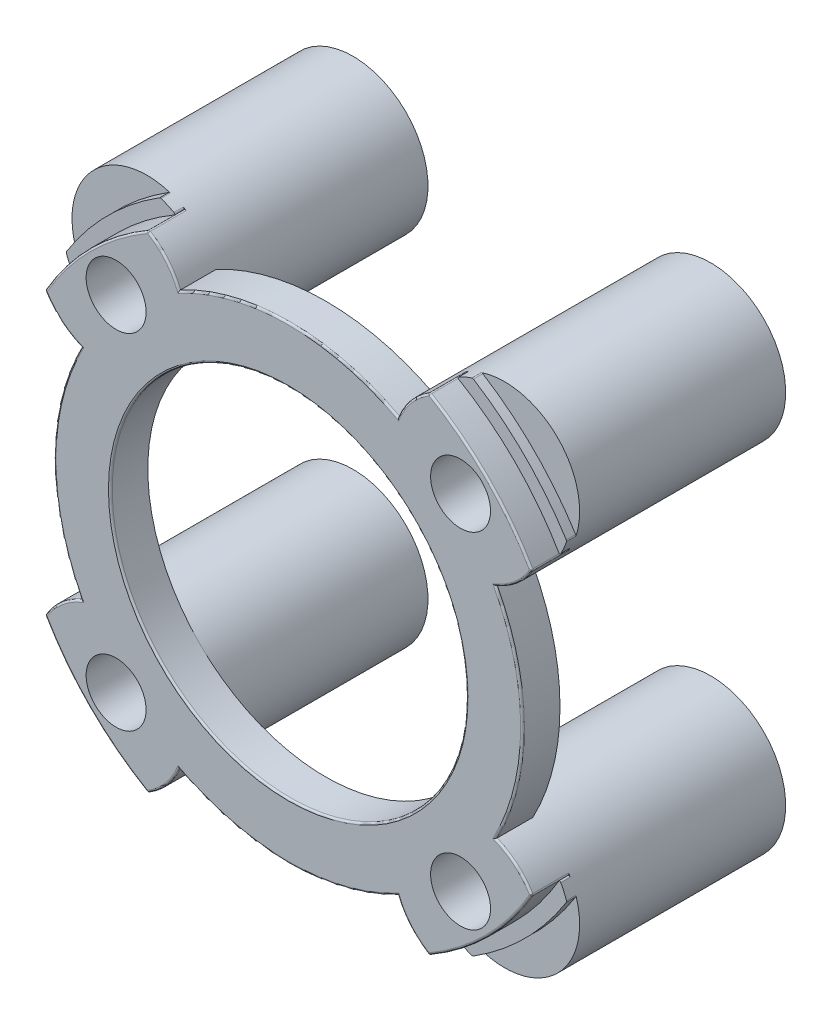
SolidWorks part; units mm, degrees
ref_plane "Front Plane" through (0, 0, 0) normal (0, 0, 1) x (1, 0, 0)
ref_plane "Top Plane" through (0, 0, 0) normal (0, 1, 0) x (1, 0, 0)
ref_plane "Right Plane" through (0, 0, 0) normal (1, 0, 0) x (0, 0, -1)
ref_plane "Output Plane" through (0, 0, 15) normal (0, 0, -1) x (-1, 0, 0)
sketch "CYC Output Sketch" plane through (0, 0, 15) normal (0, 0, 1) x (1, 0, 0)
  line L1 (9.5459, 9.5459) -> (-9.5459, 9.5459) construction
  line L2 (-9.5459, 9.5459) -> (-9.5459, -9.5459) construction
  line L3 (-9.5459, -9.5459) -> (9.5459, -9.5459) construction
  line L4 (9.5459, -9.5459) -> (9.5459, 9.5459) construction
  circle A0 centre (0, 0) radius 13.5 construction
sketch "Sketch3" plane through (0, 0, 15) normal (0, 0, -1) x (-1, 0, 0)
  circle A0 centre (-9.5459, 9.5459) radius 4
  circle A1 centre (9.5459, 9.5459) radius 4
  circle A2 centre (9.5459, -9.5459) radius 4
  circle A3 centre (-9.5459, -9.5459) radius 4
  dimension "D1" = 8
extrude "Boss-Extrude1" add sketch "Sketch3" along normal blind 11
sketch "Sketch6" plane through (0, 0, 15) normal (0, 0, 1) x (1, 0, 0)
  arc A0 (-7.5062, 12.9868) -> (-12.9868, 7.5062) centre (0, 0) ccw
  arc A5 (-11.0518, 5.8402) -> (-11.0518, -5.8402) centre (0, 0) ccw
  circle A6 centre (0, 0) radius 9.5
  arc A7 (-5.8402, 11.0518) -> (-7.5062, 12.9868) centre (-9.5459, 9.5459) ccw
  arc A8 (11.0518, 5.8402) -> (12.9868, 7.5062) centre (9.5459, 9.5459) ccw
  arc A9 (5.8402, -11.0518) -> (7.5062, -12.9868) centre (9.5459, -9.5459) ccw
  arc A10 (-11.0518, -5.8402) -> (-12.9868, -7.5062) centre (-9.5459, -9.5459) ccw
  arc A11 (5.8402, 11.0518) -> (-5.8402, 11.0518) centre (0, 0) ccw
  arc A12 (11.0518, -5.8402) -> (11.0518, 5.8402) centre (0, 0) ccw
  arc A13 (-5.8402, -11.0518) -> (5.8402, -11.0518) centre (0, 0) ccw
  arc A14 (7.5062, 12.9868) -> (5.8402, 11.0518) centre (9.5459, 9.5459) ccw
  arc A15 (12.9868, -7.5062) -> (11.0518, -5.8402) centre (9.5459, -9.5459) ccw
  arc A16 (-7.5062, -12.9868) -> (-5.8402, -11.0518) centre (-9.5459, -9.5459) ccw
  arc A17 (-12.9868, 7.5062) -> (-11.0518, 5.8402) centre (-9.5459, 9.5459) ccw
  arc A18 (12.9868, 7.5062) -> (7.5062, 12.9868) centre (0, 0) ccw
  arc A19 (7.5062, -12.9868) -> (12.9868, -7.5062) centre (0, 0) ccw
  arc A20 (-12.9868, -7.5062) -> (-7.5062, -12.9868) centre (0, 0) ccw
  dimension "D2" = 30
  dimension "D3" = 25
  dimension "D4" = 8
  dimension "D1" = 19
  dimension "D5" = 27
extrude "Boss-Extrude6" add sketch "Sketch6" along normal blind 2 contours A6 | A0 A17 A5 A10 A20 A16 A13 A9 A19 A15 A12 A8 A18 A14 A11 A7
fillet "Fillet1" radius 0.1 17 edges at (9.5, 0, 17) (0, 12.5, 17) (6.5147, 12.1558, 17) (10.6066, 10.6066, 17) (12.1558, 6.5147, 17) (12.5, 0, 17) (12.1558, -6.5147, 17) (10.6066, -10.6066, 17) (6.5147, -12.1558, 17) (0, -12.5, 17) (-6.5147, -12.1558, 17) (-10.6066, -10.6066, 17) (-12.1558, -6.5147, 17) (-12.5, 0, 17) (-12.1558, 6.5147, 17) (-10.6066, 10.6066, 17) (-6.5147, 12.1558, 17)
fillet "Fillet2" radius 0.1 16 edges at (-7.5063, -12.9669, 16.9561) (-12.9669, -7.5063, 16.9561) (-12.9669, 7.5063, 16.9561) (-7.5063, 12.9669, 16.9561) (7.5063, 12.9669, 16.9561) (7.5063, -12.9669, 16.9561) (12.9669, -7.5063, 16.9561) (12.9669, 7.5063, 16.9561) (-7.5062, -12.9868, 15.95) (-12.9868, -7.5062, 15.95) (-12.9868, 7.5062, 15.95) (-7.5062, 12.9868, 15.95) (7.5062, 12.9868, 15.95) (12.9868, -7.5062, 15.95) (7.5062, -12.9868, 15.95) (12.9868, 7.5062, 15.95)
sketch "Sketch7" plane through (0, 0, 15) normal (0, 0, -1) x (-1, 0, 0)
  arc A0 (-13.3601, -8.3409) -> (-8.3409, -13.3601) centre (0, 0) ccw
  arc A1 (8.3409, 13.3601) -> (13.3601, 8.3409) centre (9.5459, 9.5459) ccw
  arc A2 (-13.3601, 8.3409) -> (-8.3409, 13.3601) centre (-9.5459, 9.5459) ccw
  arc A3 (-8.3409, -13.3601) -> (-13.3601, -8.3409) centre (-9.5459, -9.5459) ccw
  circle A4 centre (9.5459, -9.5459) radius 4
  arc A5 (-8.3409, 13.3601) -> (-13.3601, 8.3409) centre (0, 0) ccw
  arc A6 (8.3409, -13.3601) -> (13.3601, -8.3409) centre (0, 0) ccw
  arc A7 (13.3601, 8.3409) -> (8.3409, 13.3601) centre (0, 0) ccw
  arc A8 (12.9868, 7.5062) -> (7.5062, 12.9868) centre (0, 0) ccw
  arc A9 (-7.5062, 12.9868) -> (-12.9868, 7.5062) centre (0, 0) ccw
  arc A10 (-12.9868, -7.5062) -> (-7.5062, -12.9868) centre (0, 0) ccw
  arc A11 (7.5062, -12.9868) -> (12.9868, -7.5062) centre (0, 0) ccw
  dimension "D1" = 31.5
  dimension "D2" = 8
  dimension "D3" = 30
extrude "Boss-Extrude7" add sketch "Sketch7" against normal blind 0.5 contours A8 A1 A7 | A9 A2 A5 | A10 A3 A0 | A11 A4 A6
fillet "Fillet3" radius 0.1 16 edges at (-8.3409, -13.3601, 15.25) (-13.3601, -8.3409, 15.25) (-7.5062, -12.9868, 15.25) (-12.9868, -7.5062, 15.25) (-13.3601, 8.3409, 15.25) (-8.3409, 13.3601, 15.25) (-12.9868, 7.5062, 15.25) (-7.5062, 12.9868, 15.25) (8.3409, 13.3601, 15.25) (13.3601, 8.3409, 15.25) (7.5062, 12.9868, 15.25) (12.9868, 7.5062, 15.25) (13.3601, -8.3409, 15.25) (8.3409, -13.3601, 15.25) (12.9868, -7.5062, 15.25) (7.5062, -12.9868, 15.25)
sketch "Sketch8" plane through (0, 0, 17) normal (0, 0, 1) x (1, 0, 0)
  line L0 (0, 0) -> (9.1924, 9.1924) construction
  line L1 (0, 0) -> (13, 0) construction
  circle A0 centre (0, 0) radius 13 construction
  circle A1 centre (9.1924, 9.1924) radius 1.6
  circle A2 centre (9.1924, -9.1924) radius 1.6
  circle A3 centre (-9.1924, -9.1924) radius 1.6
  circle A4 centre (-9.1924, 9.1924) radius 1.6
  point P16 (0, 0)
  dimension "D1" = 26
  dimension "D2" = 45
  dimension "D3" = 3.2
  dimension "D4" = 4
extrude "Cut-Extrude1" cut sketch "Sketch8" against normal through all
sketch "Sketch9" plane through (0, 0, 17) normal (0, 0, 1) x (1, 0, 0)
  circle A0 centre (9.1924, 9.1924) radius 2.75
  circle A1 centre (9.1924, -9.1924) radius 2.75
  circle A2 centre (-9.1924, -9.1924) radius 2.75
  circle A3 centre (-9.1924, 9.1924) radius 2.75
  point P12 (0, 0)
  dimension "D1" = 5.5
  dimension "D2" = 4
extrude "Cut-Extrude2" cut sketch "Sketch9" along normal blind 3 from surface at -13 starting at face at (10.7924, 9.1924, 4)
equation "\"RingPinShaft\"= 5"
equation "\"CenterBearingOut\"=32.125"
equation "\"RingPostIn\"=5.125"
equation "\"CamBearingOut\"=15.125"
equation "\"DiskOutputShaft\"=10"
equation "\"CenterShaft\"=25"
equation "\"Eccentricity\"=2"
equation "\"CycCamShaft\"=10"
equation "\"D2@Sketch6\"=\"OutputBearing\""
equation "\"OutputBearing\"=30"
